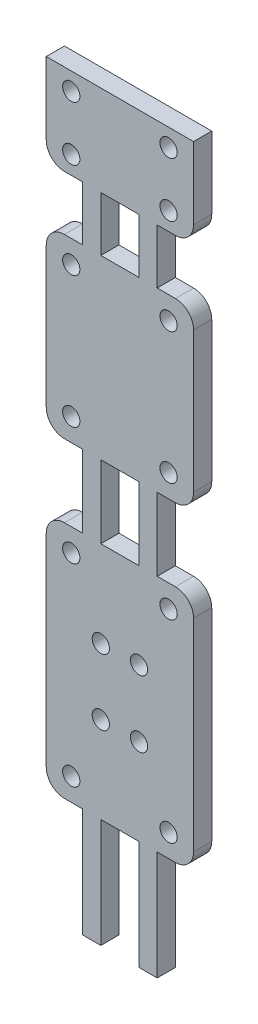
SolidWorks part; units mm, degrees
ref_plane "Front Plane" through (0, 0, 0) normal (0, 0, 1) x (1, 0, 0)
ref_plane "Top Plane" through (0, 0, 0) normal (0, 1, 0) x (1, 0, 0)
ref_plane "Right Plane" through (0, 0, 0) normal (1, 0, 0) x (0, 0, -1)
sketch "Sketch3" plane through (0, 0, 0) normal (0, 0, 1) x (1, 0, 0)
  line L0 (0, 94.0064) -> (0, 86.0614)
  line L1 (16.2, 94.0064) -> (16.2, 86.0614)
  line L2 (0, -0.1536) -> (16.2, -0.1536) construction
  line L3 (0, 76.0614) -> (0, 60.6064)
  line L4 (0, 94.0064) -> (16.2, 94.0064)
  line L5 (0, 12.3464) -> (4, 12.3464) construction
  line L6 (2, 58.6064) -> (4, 58.6064)
  line L7 (16.2, 76.0614) -> (16.2, 60.6064)
  line L8 (0, 48.6064) -> (0, 26.3464)
  line L9 (16.2, 48.6064) -> (16.2, 26.3464)
  line L10 (16.2, 12.3464) -> (16.2, -0.1536) construction
  line L11 (0, 12.3464) -> (0, -0.1536) construction
  line L12 (6, 12.3464) -> (6, 24.3464)
  line L13 (6, 24.3464) -> (10.2, 24.3464)
  line L14 (4, 12.3464) -> (4, 24.3464)
  line L15 (6, 12.3464) -> (10.2, 12.3464) construction
  line L16 (4, 50.6064) -> (4, 58.6064)
  line L17 (4, 78.0614) -> (4, 84.0614)
  line L18 (6, 50.6064) -> (6, 58.6064)
  line L19 (6, 78.0614) -> (6, 84.0614)
  line L20 (6, 84.0614) -> (10.2, 84.0614)
  line L21 (6, 78.0614) -> (10.2, 78.0614)
  line L22 (6, 58.6064) -> (10.2, 58.6064)
  line L23 (6, 50.6064) -> (10.2, 50.6064)
  line L24 (8.1, 94.0064) -> (8.1, -0.1536) construction
  line L25 (12.2, 50.6064) -> (12.2, 58.6064)
  line L26 (2, 50.6064) -> (4, 50.6064)
  line L27 (2, 24.3464) -> (4, 24.3464)
  line L28 (10.2, 12.3464) -> (10.2, 24.3464)
  line L29 (12.2, 12.3464) -> (12.2, 24.3464)
  line L30 (2, 78.0614) -> (4, 78.0614)
  line L31 (10.2, 50.6064) -> (10.2, 58.6064)
  line L32 (2, 84.0614) -> (4, 84.0614)
  line L33 (12.2, 78.0614) -> (12.2, 84.0614)
  line L34 (10.2, 78.0614) -> (10.2, 84.0614)
  line L35 (12.2, 84.0614) -> (14.2, 84.0614)
  line L36 (12.2, 78.0614) -> (14.2, 78.0614)
  line L37 (12.2, 58.6064) -> (14.2, 58.6064)
  line L38 (12.2, 50.6064) -> (14.2, 50.6064)
  line L39 (12.2, 12.3464) -> (16.2, 12.3464) construction
  line L40 (12.2, 24.3464) -> (14.2, 24.3464)
  line L41 (4, 12.3464) -> (6, 12.3464)
  line L42 (10.2, 12.3464) -> (12.2, 12.3464)
  circle A0 centre (6, 33.8464) radius 0.95
  circle A1 centre (10.2, 33.8464) radius 0.95
  circle A2 centre (2.75, 86.0614) radius 0.95
  circle A3 centre (10.2, 41.1664) radius 0.95
  circle A4 centre (13.45, 48.1064) radius 0.95
  circle A5 centre (2.75, 92.0614) radius 0.95
  circle A6 centre (13.45, 86.0614) radius 0.95
  circle A7 centre (2.75, 61.1064) radius 0.95
  arc A8 (14.2, 24.3464) -> (16.2, 26.3464) centre (14.2, 26.3464) ccw
  arc A9 (16.2, 48.6064) -> (14.2, 50.6064) centre (14.2, 48.6064) ccw
  arc A10 (2, 50.6064) -> (0, 48.6064) centre (2, 48.6064) ccw
  arc A11 (0, 26.3464) -> (2, 24.3464) centre (2, 26.3464) ccw
  arc A12 (0, 60.6064) -> (2, 58.6064) centre (2, 60.6064) ccw
  arc A13 (14.2, 58.6064) -> (16.2, 60.6064) centre (14.2, 60.6064) ccw
  arc A14 (16.2, 76.0614) -> (14.2, 78.0614) centre (14.2, 76.0614) ccw
  arc A15 (0, 76.0614) -> (2, 78.0614) centre (2, 76.0614) cw
  circle A16 centre (2.85, 9.8464) radius 0.95 construction
  circle A17 centre (13.35, 9.8464) radius 0.95 construction
  circle A18 centre (13.35, 3.8464) radius 0.95 construction
  circle A19 centre (2.85, 3.8464) radius 0.95 construction
  circle A20 centre (13.45, 61.1064) radius 0.95
  circle A21 centre (2.75, 75.5614) radius 0.95
  circle A22 centre (13.45, 26.8464) radius 0.95
  circle A23 centre (13.45, 75.5614) radius 0.95
  circle A24 centre (13.45, 92.0614) radius 0.95
  circle A25 centre (2.75, 26.8464) radius 0.95
  circle A26 centre (6, 41.1064) radius 0.95
  circle A27 centre (2.75, 48.1064) radius 0.95
  arc A28 (16.2, 86.0614) -> (14.2, 84.0614) centre (14.2, 86.0614) cw
  arc A29 (2, 84.0614) -> (0, 86.0614) centre (2, 86.0614) cw
  point P76 (16.2, 24.3464)
  point P80 (16.2, 50.6064)
  point P84 (0, 50.6064)
  point P88 (0, 24.3464)
  point P95 (0, 58.6064)
  point P99 (16.2, 58.6064)
  point P102 (16.2, 78.0614)
  point P105 (0, 78.0614)
  point P108 (16.2, 84.0614)
  point P111 (0, 84.0614)
  dimension "D49" = 1.9
  dimension "D50" = 2
  dimension "D1" = 2.5
  dimension "D2" = 9.5
  dimension "D3" = 2.5
  dimension "D4" = 9.5
  dimension "D5" = 6
  dimension "D6" = 2.75
  dimension "D7" = 2.75
  dimension "D8" = 6
  dimension "D9" = 2.5
  dimension "D10" = 2.5
  dimension "D11" = 9.5
  dimension "D12" = 9.44
  dimension "D13" = 2.75
  dimension "D14" = 6
  dimension "D15" = 2.75
  dimension "D16" = 6
  dimension "D17" = 12
  dimension "D19" = 4
  dimension "D21" = 6
  dimension "D22" = 4
  dimension "D23" = 2.85
  dimension "D24" = 2.85
  dimension "D25" = 26.26
  dimension "D26" = 16.2
  dimension "D27" = 8
  dimension "D28" = 2.5
  dimension "D29" = 2.5
  dimension "D30" = 2.75
  dimension "D31" = 2.75
  dimension "D34" = 2.5
  dimension "D35" = 2.5
  dimension "D36" = 2.75
  dimension "D37" = 2.75
  dimension "D38" = 19.455
  dimension "D39" = 6
  dimension "D40" = 2
  dimension "D41" = 2
  dimension "D42" = 2.75
  dimension "D43" = 2.75
  dimension "D46" = 2.75
  dimension "D47" = 2.75
  dimension "D48" = 9.945
  dimension "D32" = 6
  dimension "D33" = 6
  dimension "D18" = 2.5
  dimension "D44" = 2.5
  dimension "D20" = 6
  dimension "D45" = 4
extrude "Boss-Extrude3" add sketch "Sketch3" along normal blind 2
sketch "Sketch4" plane through (0, 0, 2) normal (0, 0, 1) x (1, 0, 0)
  line L0 (4, 84.0614) -> (12.2, 84.0614)
  line L1 (12.2, 84.0614) -> (12.2, 78.0614)
  line L2 (12.2, 78.0614) -> (4, 78.0614)
  line L3 (4, 78.0614) -> (4, 84.0614)
  line L4 (4, 58.6064) -> (12.2, 58.6064)
  line L5 (12.2, 58.6064) -> (12.2, 50.6064)
  line L6 (12.2, 50.6064) -> (4, 50.6064)
  line L7 (4, 50.6064) -> (4, 58.6064)
  line L8 (4, 24.3464) -> (12.2, 24.3464)
  line L9 (12.2, 24.3464) -> (12.2, 12.3464)
  line L10 (12.2, 12.3464) -> (4, 12.3464)
  line L11 (4, 12.3464) -> (4, 24.3464)
extrude "Cut-Extrude1" [suppressed] cut sketch "Sketch4" against normal up to surface (2 mm away) up to face at (1.8, 92.0614, 0)
equation "\"D25@Sketch3\"= \"HL@parametersSketch@prostheticParameters.SLDPRT\" * 0.196 - 4 - 6'Index PIP length"
equation "\"D26@Sketch3\"= \"fingerWidth@parametersSketch@prostheticParameters.SLDPRT\"'Index Width"
equation "\"D38@Sketch3\"= \"HL@parametersSketch@prostheticParameters.SLDPRT\" * 0.143 - 3 - 4 'Index MIP Length"
equation "\"D48@Sketch3\"= \"HL@parametersSketch@prostheticParameters.SLDPRT\" * 0.097 - 3 - 5'Index DIP Length - Gap Fingertip"
equation "\"D49@Sketch3\"= 1.5 + \"tol1@parametersSketch@prostheticParameters.SLDPRT\""
